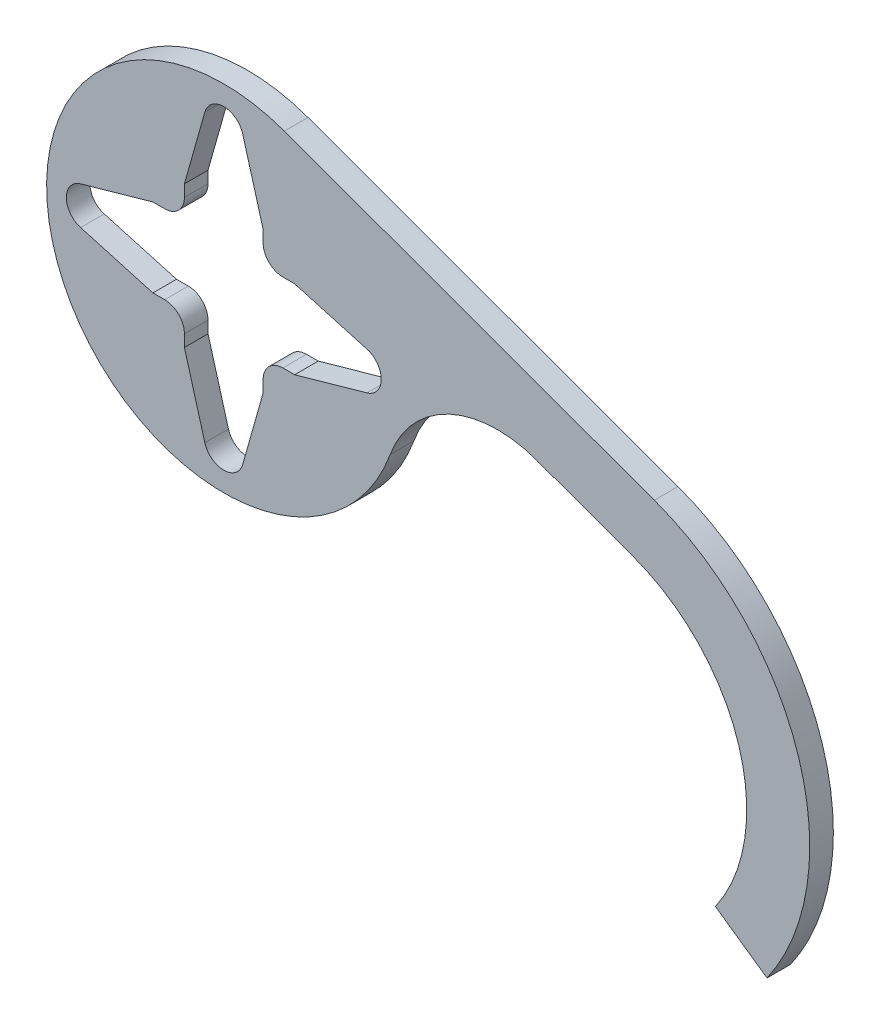
SolidWorks part; units mm, degrees
ref_plane "Front Plane" through (0, 0, 0) normal (0, 0, 1) x (1, 0, 0)
ref_plane "Top Plane" through (0, 0, 0) normal (0, 1, 0) x (1, 0, 0)
ref_plane "Right Plane" through (0, 0, 0) normal (1, 0, 0) x (0, 0, -1)
sketch "Sketch1" plane through (0, 0, 0) normal (0, 0, 1) x (1, 0, 0)
  line L0 (-5, 5) -> (-5, 9)
  line L8 (5, -5) -> (-5, -5)
  line L9 (5, -5) -> (5, 5)
  line L10 (5, 5) -> (-5, 5)
  line L11 (-5, -5) -> (-5, 5)
  line L12 (5, -5) -> (-5, 5) construction
  line L13 (5, 5) -> (-5, -5) construction
  line L14 (-5, 9) -> (-2.4058, 18.1799)
  line L15 (0, -55) -> (0, 55) construction
  line L16 (9, 5) -> (18.1799, 2.4058)
  line L17 (5, 5) -> (5, 9)
  line L18 (55, 0) -> (-55, 0) construction
  line L19 (5, -5) -> (5, -9)
  line L20 (-5, -9) -> (-2.4058, -18.1799)
  line L21 (5, -9) -> (2.4058, -18.1799)
  line L22 (-5, -5) -> (-5, -9)
  line L23 (5, -5) -> (9, -5)
  line L24 (9, -5) -> (18.1799, -2.4058)
  line L25 (-9, -5) -> (-18.1799, -2.4058)
  line L26 (5, 5) -> (9, 5)
  line L27 (-5, -5) -> (-9, -5)
  line L28 (-9, 5) -> (-18.1799, 2.4058)
  line L29 (5, 9) -> (2.4058, 18.1799)
  line L30 (-5, 5) -> (-9, 5)
  line L31 (0, 22.5) -> (-22.5, 0)
  line L32 (-22.5, 0) -> (-22.5, 22.5)
  line L33 (-22.5, 22.5) -> (0, 22.5)
  line L34 (-27.0416, 0) -> (-22.5, 0)
  line L35 (-22.5, 22.5) -> (-152.5, 22.5)
  line L36 (-22.5, 22.5) -> (-22.5, 0)
  line L37 (-22.5, 0) -> (-107.5, 0)
  line L38 (-152.5, 22.5) -> (-152.5, -11.5)
  line L41 (-22.5, 0) -> (-22.125, -4.0909)
  line L44 (-127.5, -11.5) -> (-127.5, -26.5)
  line L45 (-127.5, -26.5) -> (-107.5, -26.5)
  line L46 (-107.5, 0) -> (-107.5, -26.5)
  line L48 (-127.5, -11.5) -> (-152.5, -11.5)
  circle A0 centre (0, 0) radius 22.5
  circle A1 centre (0, 17.5) radius 2.5
  circle A2 centre (0, -17.5) radius 2.5
  circle A3 centre (17.5, 0) radius 2.5
  circle A4 centre (-17.5, 0) radius 2.5
  circle A5 centre (-7.5, 7.5) radius 2.5
  circle A6 centre (-7.5, -7.5) radius 2.5
  circle A7 centre (7.5, 7.5) radius 2.5
  circle A8 centre (7.5, -7.5) radius 2.5
  arc A9 (-27.0416, 0) -> (-22.125, -4.0909) centre (-27.0416, -5) cw
  dimension "D1" = 45
  dimension "D3" = 5
  dimension "D5" = 12.5
  dimension "D6" = 5
  dimension "D9" = 5
  dimension "D11" = 5
  dimension "D2" = 10
  dimension "D4" = 4
  dimension "D7" = 4
  dimension "D8" = 12.5
  dimension "D10" = 130
  dimension "D12" = 15
  dimension "D13" = 20
  dimension "D14" = 25
  dimension "D15" = 34
extrude "Boss-Extrude1" add sketch "Sketch1" along normal blind 3 contours A0 A4 L30 L0 A1 L17 L26 A3 L23 L19 A2 L22 L27 | A5 | A7 | A8 | A6 | L33 L31 L32 | L36 L37 L46 L45 L44 L48 L38 L35 | L41 A9 L34 region at (15.4599, 15.4599, 0)
sketch "Sketch3" [suppressed] plane through (0, 0, 3) normal (0, 0, 1) x (1, 0, 0)
  circle A0 centre (0, 0) radius 5
  circle A1 centre (0, 0) radius 22.5
  arc A2 (-22.125, -4.0909) -> (0, 22.5) centre (0, 0) ccw construction
  dimension "D1" = 10
extrude "Boss-Extrude2" [suppressed] add sketch "Sketch3" against normal up to surface (3 mm away) up to face at (-88.341, -6.4219, 0)
sketch "Sketch4" plane through (0, 0, 3) normal (0, 0, 1) x (1, 0, 0)
  line L0 (-152.5, 22.5) -> (0, 22.5) construction
  line L3 (-152.5, 22.5) -> (0, 22.5)
  line L7 (-27.0416, 0) -> (-107.5, 0) construction
  line L8 (-107.5, 0) -> (-107.5, -26.5) construction
  line L9 (-127.5, -26.5) -> (-107.5, -26.5) construction
  line L10 (-127.5, -11.5) -> (-127.5, -26.5) construction
  line L11 (-127.5, -11.5) -> (-152.5, -11.5) construction
  line L12 (-152.5, 22.5) -> (-152.5, -11.5) construction
  line L13 (-27.0416, 0) -> (-107.5, 0)
  line L14 (-107.5, 0) -> (-107.5, -26.5)
  line L15 (-127.5, -26.5) -> (-107.5, -26.5)
  line L16 (-127.5, -11.5) -> (-127.5, -26.5)
  line L17 (-127.5, -11.5) -> (-152.5, -11.5)
  line L18 (-152.5, 22.5) -> (-152.5, -11.5)
  arc A0 (0, 22.5) -> (-22.125, -4.0909) centre (0, 0) ccw
  arc A1 (-22.125, -4.0909) -> (0, 22.5) centre (0, 0) ccw construction
  arc A2 (-22.125, -4.0909) -> (-27.0416, 0) centre (-27.0416, -5) ccw construction
  arc A3 (-22.125, -4.0909) -> (-27.0416, 0) centre (-27.0416, -5) ccw
extrude "Cut-Extrude1" cut sketch "Sketch4" against normal through all
sketch "Sketch5" [suppressed] plane through (0, 0, 0) normal (0, 0, -1) x (-1, 0, 0)
  circle A0 centre (0, 0) radius 5
  circle A2 centre (0, 0) radius 22.5
  circle A5 centre (0, 0) radius 22.5 construction
  dimension "D1" = 10
extrude "Boss-Extrude3" [suppressed] add sketch "Sketch5" against normal up to surface (3 mm away) up to face at (22.5, 0, 3)
sketch "Sketch6" plane through (0, 0, 3) normal (0, 0, 1) x (1, 0, 0)
  line L0 (7.6955, 21.1431) -> (54.6801, 4.0421)
  line L1 (68.994, -41.356) -> (62.4408, -36.7674)
  line L2 (39.7279, 0.9708) -> (51.9439, -3.4755)
  line L3 (7.6955, 21.1431) -> (0, 0) construction
  line L4 (0, 0) -> (21.1431, -7.6955) construction
  line L5 (0, -1000) -> (0, 49000) construction
  arc A0 (54.6801, 4.0421) -> (68.994, -41.356) centre (44.4195, -24.1487) cw
  arc A2 (21.1431, -7.6955) -> (7.6955, 21.1431) centre (0, 0) ccw
  arc A3 (51.9439, -3.4755) -> (62.4408, -36.7674) centre (44.4195, -24.1487) cw
  circle A4 centre (0, 0) radius 22.5 construction
  arc A5 (21.1431, -7.6955) -> (39.7279, 0.9708) centre (34.7686, -12.6547) cw
  dimension "D2" = 22
  dimension "D1" = 8
  dimension "D3" = 50
  dimension "D4" = 20
  dimension "D5" = 15
extrude "Boss-Extrude4" add sketch "Sketch6" against normal up to surface (3 mm away) up to face at (22.5, 0, 0)
sketch "Sketch7" [suppressed] plane through (0, 0, 3) normal (0, 0, 1) x (1, 0, 0)
  line L0 (54.6801, 4.0421) -> (51.9439, -3.4755)
  line L1 (54.6801, 4.0421) -> (7.6955, 21.1431) construction
  line L2 (39.7279, 0.9708) -> (51.9439, -3.4755) construction
  line L3 (39.7279, 0.9708) -> (51.9439, -3.4755)
  line L4 (54.6801, 4.0421) -> (7.6955, 21.1431)
  arc A0 (39.7279, 0.9708) -> (21.1431, -7.6955) centre (34.7686, -12.6547) ccw construction
  arc A1 (7.6955, 21.1431) -> (21.1431, -7.6955) centre (0, 0) ccw construction
  arc A2 (39.7279, 0.9708) -> (21.1431, -7.6955) centre (34.7686, -12.6547) ccw
  arc A3 (7.6955, 21.1431) -> (21.1431, -7.6955) centre (0, 0) ccw
extrude "Cut-Extrude2" [suppressed] cut sketch "Sketch7" against normal through all
ref_plane "Plane1" through (0, 0, 1.5) normal (0, 0, -1) x (-1, 0, 0)
